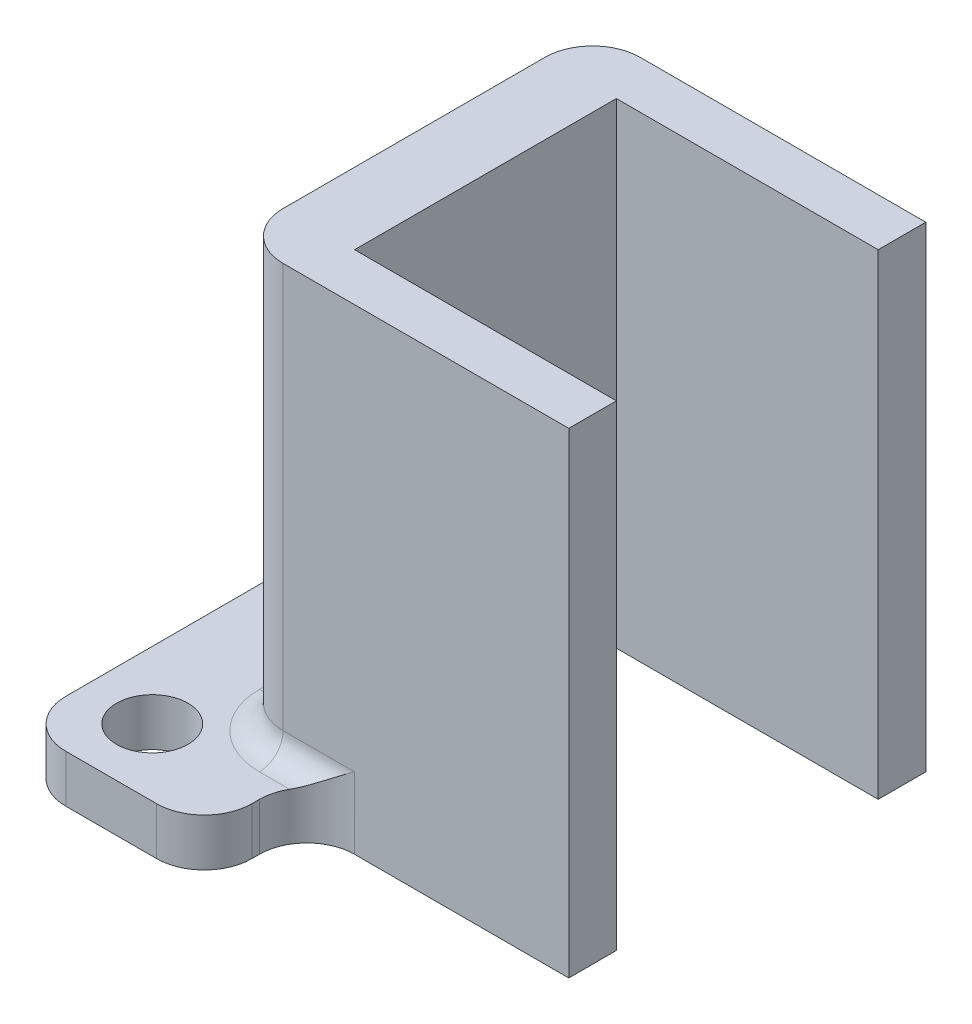
SolidWorks part; units mm, degrees
ref_plane "Plan de face" through (0, 0, 0) normal (0, 0, 1) x (1, 0, 0)
ref_plane "Plan de dessus" through (0, 0, 0) normal (0, 1, 0) x (1, 0, 0)
ref_plane "Plan de droite" through (0, 0, 0) normal (1, 0, 0) x (0, 0, -1)
sketch "Sketch1" plane through (0, 0, 0) normal (0, 1, 0) x (1, 0, 0)
  line L0 (-5, 14.5) -> (-5, -3.5) construction
  line L1 (0, 0) -> (11, 0)
  line L2 (0, 0) -> (0, 11)
  line L3 (0, 11) -> (11, 11)
  line L4 (11, 0) -> (11, 11)
  line L5 (11, 13) -> (-3, 13)
  line L6 (11, 13) -> (11, -2)
  line L7 (11, -2) -> (-3, -2)
  line L8 (-3, 13) -> (-3, -2)
  line L9 (0, 17.3159) -> (-7.816, 17.3159)
  line L10 (0, 17.3159) -> (0, -6.3159)
  line L11 (0, -6.3159) -> (-7.816, -6.3159)
  line L12 (-7.816, 17.3159) -> (-7.816, -6.3159)
  circle A2 centre (-5, 14.5) radius 1.5
  circle A3 centre (-5, -3.5) radius 1.5
  point P9 (11, 5.5)
  point P10 (11, 5.5)
  point P17 (-7.816, 5.5)
  point P18 (0, 5.5)
  point P21 (-5, 5.5)
  point P22 (0, 17.3159)
  dimension "D5" = 3
  dimension "D6" = 3
  dimension "D1" = 11
  dimension "D2" = 11
  dimension "D3" = 15
  dimension "D4" = 14
  dimension "D7" = 18
  dimension "D9" = 5
extrude "Boss-Extrude1" add sketch "Sketch1" along normal blind 2
extrude "Boss-Extrude2" add sketch "Sketch1<3>" along normal blind 20 contours L10 L5 L8 L7 L2 | L1 L10 L7 L6 | L5 L10 L3 L6 region at (-1.5, 0, -5.5) region at (5.5, 0, 1) region at (5.5, 0, -12)
sketch "Sketch1<3>" plane through (0, 0, 0) normal (0, 1, 0) x (1, 0, 0) same geometry as "Sketch1"
fillet "Fillet2" radius 2 8 edges at (-3, 11, 2) (-3, 11, -13) (0, 1, 6.3159) (0, 1, 2) (-7.816, 1, 6.3159) (-7.816, 1, -17.3159) (0, 1, -17.3159) (0, 1, -13)
fillet "Fillet3" radius 1 5 edges at (0.5, 2, 2) (0.5, 2, -13) (-2.4142, 2, 1.4142) (-2.4142, 2, -12.4142) (-3, 2, -5.5)
